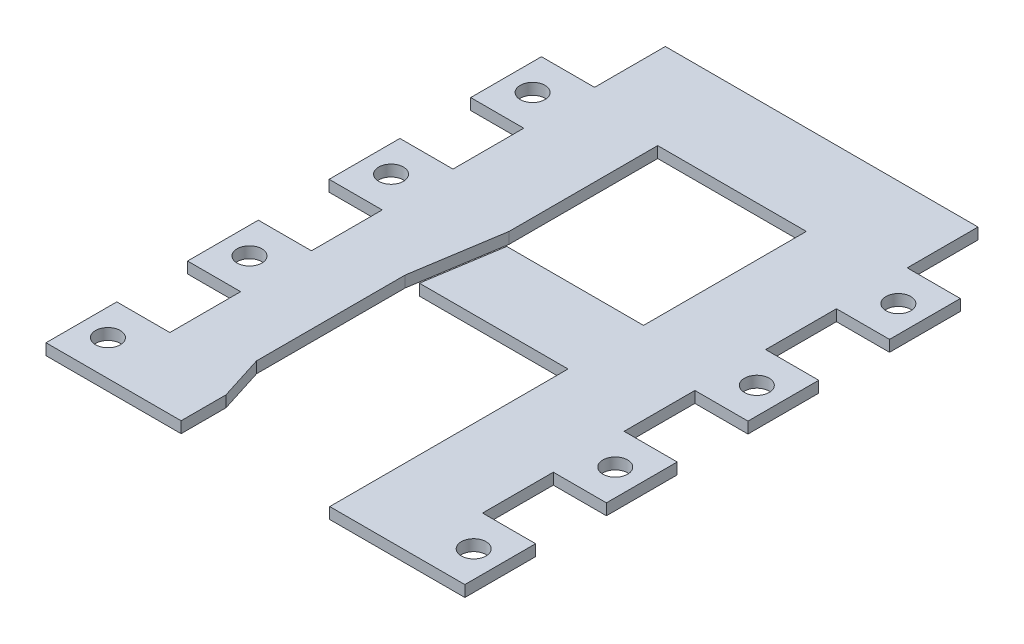
SolidWorks part; units mm, degrees
ref_plane "Front Plane" through (0, 0, 0) normal (0, 0, 1) x (1, 0, 0)
ref_plane "Top Plane" through (0, 0, 0) normal (0, 1, 0) x (1, 0, 0)
ref_plane "Right Plane" through (0, 0, 0) normal (1, 0, 0) x (0, 0, -1)
sketch "Sketch1" plane through (0, 0, 0) normal (0, 1, 0) x (1, 0, 0)
  line L0 (44.175, 25.3333) -> (44.175, 0) construction
  line L1 (0, 0) -> (88.35, 0)
  line L2 (0, 0) -> (0, 160)
  line L3 (0, 160) -> (88.35, 160)
  line L4 (88.35, 0) -> (88.35, 160)
  line L5 (23.175, 134.6667) -> (65.175, 134.6667)
  line L6 (23.175, 134.6667) -> (23.175, 92.6667)
  line L7 (23.175, 92.6667) -> (65.175, 92.6667)
  line L8 (65.175, 134.6667) -> (65.175, 92.6667)
  line L9 (23.175, 67.3333) -> (65.175, 67.3333)
  line L10 (23.175, 67.3333) -> (23.175, 25.3333)
  line L11 (23.175, 25.3333) -> (65.175, 25.3333)
  line L12 (65.175, 67.3333) -> (65.175, 25.3333)
  line L13 (44.175, 134.6667) -> (44.175, 160) construction
  line L14 (44.175, 67.3333) -> (44.175, 92.6667) construction
  line L15 (23.175, 92.6667) -> (19.175, 67.3333)
  line L16 (23.175, 25.3333) -> (27.175, 25.3333)
  line L17 (23.175, 25.3333) -> (23.175, 0)
  line L18 (23.175, 0) -> (27.175, 0)
  line L19 (27.175, 25.3333) -> (27.175, 0)
  line L20 (65.175, 25.3333) -> (61.175, 25.3333)
  line L21 (65.175, 25.3333) -> (65.175, 0)
  line L22 (65.175, 0) -> (61.175, 0)
  line L23 (61.175, 25.3333) -> (61.175, 0)
  line L24 (19.175, 67.3333) -> (19.175, 25.3333)
  line L25 (19.175, 25.3333) -> (23.175, 12.6667)
  line L26 (27.175, 92.6667) -> (23.175, 67.3333)
  line L27 (19.175, 67.3333) -> (23.175, 67.3333) construction
  line L28 (27.175, 92.6667) -> (23.175, 92.6667)
  line L29 (23.175, 12.6667) -> (23.175, 25.3333)
  line L30 (65.175, 92.6667) -> (65.175, 88.6667)
  line L31 (65.175, 88.6667) -> (26.5434, 88.6667)
  point P13 (44.175, 67.3333)
  point P14 (44.175, 92.6667)
  point P15 (44.175, 134.6667)
  point P16 (44.175, 160)
  dimension "D1" = 88.35
  dimension "D2" = 160
  dimension "D3" = 42
  dimension "D4" = 4
extrude "Boss-Extrude1" add sketch "Sketch1" along normal blind 3.175 contours L30 L31 L26 L9 L12 L21 L1 L4 L3 L2 L17 L25 L24 L15 L6 L5 L8 region at (44.8649, 0, -88.4824)
sketch "Sketch3" plane through (0, 3.175, 0) normal (0, 1, 0) x (1, 0, 0)
  line L0 (0, 0) -> (0, 160) construction
  line L1 (0, 140) -> (-15, 140)
  line L2 (0, 140) -> (0, 120)
  line L3 (0, 120) -> (-15, 120)
  line L4 (-15, 140) -> (-15, 120)
  line L5 (0, 100) -> (0, 80)
  line L6 (0, 100) -> (-15, 100)
  line L7 (-15, 100) -> (-15, 80)
  line L8 (0, 80) -> (-15, 80)
  line L9 (0, 60) -> (0, 40)
  line L10 (0, 60) -> (-15, 60)
  line L11 (-15, 60) -> (-15, 40)
  line L12 (0, 40) -> (-15, 40)
  line L13 (0, 20) -> (0, 0)
  line L14 (0, 20) -> (-15, 20)
  line L15 (-15, 20) -> (-15, 0)
  line L16 (0, 0) -> (-15, 0)
  line L17 (-15, 0) -> (-15, -20) construction
  line L19 (44.175, 160) -> (44.175, 134.6667) construction
  line L20 (0, 160) -> (88.35, 160) construction
  line L21 (23.175, 134.6667) -> (65.175, 134.6667) construction
  line L22 (103.35, 0) -> (103.35, -20) construction
  line L23 (88.35, 0) -> (103.35, 0)
  line L24 (103.35, 20) -> (103.35, 0)
  line L25 (88.35, 20) -> (103.35, 20)
  line L26 (88.35, 20) -> (88.35, 0)
  line L27 (88.35, 40) -> (103.35, 40)
  line L28 (103.35, 60) -> (103.35, 40)
  line L29 (88.35, 60) -> (103.35, 60)
  line L30 (88.35, 60) -> (88.35, 40)
  line L31 (88.35, 80) -> (103.35, 80)
  line L32 (103.35, 100) -> (103.35, 80)
  line L33 (88.35, 100) -> (103.35, 100)
  line L34 (88.35, 100) -> (88.35, 80)
  line L35 (103.35, 140) -> (103.35, 120)
  line L36 (88.35, 120) -> (103.35, 120)
  line L37 (88.35, 140) -> (88.35, 120)
  line L38 (88.35, 140) -> (103.35, 140)
  line L39 (-15, 140) -> (-15, 160) construction
  circle A0 centre (-7.5, 130) radius 3.5
  circle A1 centre (-7.5, 90) radius 3.5
  circle A2 centre (-7.5, 50) radius 3.5
  circle A3 centre (-7.5, 10) radius 3.5
  circle A4 centre (95.85, 10) radius 3.5
  circle A5 centre (95.85, 50) radius 3.5
  circle A6 centre (95.85, 90) radius 3.5
  circle A7 centre (95.85, 130) radius 3.5
  point P6 (-7.5, 140)
  point P12 (-15, 130)
  dimension "D3" = 7
  dimension "D1" = 20
  dimension "D2" = 15
  dimension "D4" = 4
extrude "Boss-Extrude3" add sketch "Sketch3" against normal up to surface (3.175 mm away) up to face at (38.6355, 0, -68.7083)
sketch "Sketch4" plane through (0, 3.175, 0) normal (0, 1, 0) x (1, 0, 0)
  line L0 (-15, 0) -> (23.175, 0) construction
  line L1 (0, 0) -> (23.175, 0)
  line L2 (0, 0) -> (0, -6.096)
  line L3 (0, -6.096) -> (23.175, -6.096)
  line L4 (23.175, 0) -> (23.175, -6.096)
  line L5 (65.175, 0) -> (103.35, 0) construction
  line L6 (65.175, 0) -> (88.35, 0)
  line L7 (65.175, 0) -> (65.175, -6.096)
  line L8 (65.175, -6.096) -> (88.35, -6.096)
  line L9 (88.35, 0) -> (88.35, -6.096)
  dimension "D1" = 88.35
  dimension "D2" = 6.096
extrude "Boss-Extrude4" add sketch "Sketch4" against normal up to surface (3.175 mm away) up to face at (42.1606, 0, -75.8939)
sketch "Sketch5" plane through (0, 3.175, 0) normal (0, 1, 0) x (1, 0, 0)
  line L1 (0, 0) -> (88.35, 0)
  line L2 (0, 0) -> (0, -6.096)
  line L3 (0, -6.096) -> (88.35, -6.096)
  line L4 (88.35, 0) -> (88.35, -6.096)
extrude "Cut-Extrude1" cut sketch "Sketch5" against normal through all
